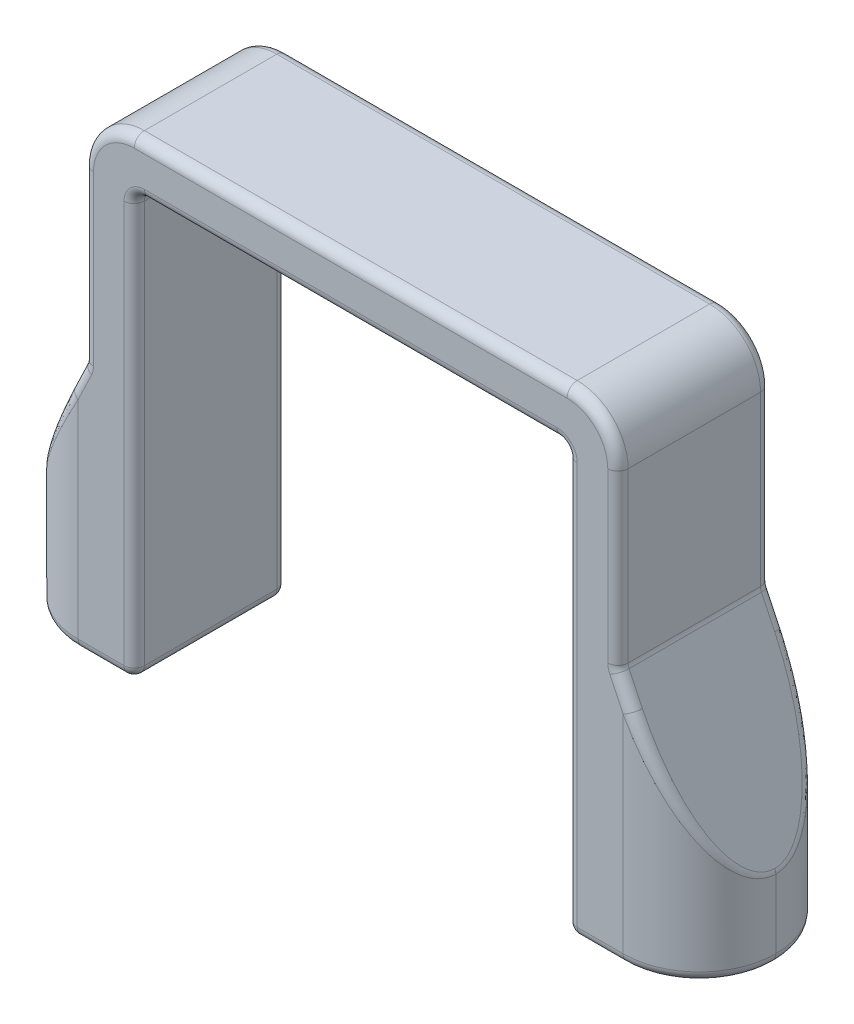
SolidWorks part; units mm, degrees
ref_plane "Front Plane" through (0, 0, 0) normal (0, 0, 1) x (1, 0, 0)
ref_plane "Top Plane" through (0, 0, 0) normal (0, 1, 0) x (1, 0, 0)
ref_plane "Right Plane" through (0, 0, 0) normal (1, 0, 0) x (0, 0, -1)
sketch "Sketch2" plane through (0, 0, 0) normal (0, 0, 1) x (1, 0, 0)
  line L0 (34.25, -20.75) -> (34.25, -12.75)
  line L5 (21.25, -20.75) -> (-21.25, -20.75)
  line L6 (0, -20.75) -> (0, 20.75) construction
  line L11 (21.25, 20.75) -> (-21.25, 20.75)
  line L12 (-21.25, -20.75) -> (-21.25, 20.75)
  line L13 (-26.25, 25.75) -> (26.25, 25.75)
  line L14 (-26.25, 25.75) -> (-26.25, 20.75)
  line L15 (-26.25, 20.75) -> (26.25, 20.75)
  line L16 (0, 25.75) -> (0, 20.75)
  line L17 (-21.25, -20.75) -> (-26.25, -20.75)
  line L18 (-21.25, -20.75) -> (-21.25, 20.75)
  line L19 (-21.25, 20.75) -> (-26.25, 20.75)
  line L20 (-26.25, -20.75) -> (-26.25, 20.75)
  line L21 (-26.25, -20.75) -> (-34.25, -20.75)
  line L22 (-26.25, -20.75) -> (-26.25, -12.75)
  line L23 (-26.25, -12.75) -> (-34.25, -12.75)
  line L24 (-34.25, -20.75) -> (-34.25, -12.75)
  line L25 (26.25, -12.75) -> (34.25, -12.75)
  line L26 (26.25, -20.75) -> (26.25, -12.75)
  line L27 (26.25, -20.75) -> (34.25, -20.75)
  line L28 (26.25, -20.75) -> (26.25, 20.75)
  line L29 (21.25, 20.75) -> (26.25, 20.75)
  line L30 (21.25, -20.75) -> (21.25, 20.75)
  line L31 (21.25, -20.75) -> (26.25, -20.75)
  line L32 (26.25, 25.75) -> (26.25, 20.75)
  line L33 (21.25, -20.75) -> (21.25, 20.75)
  line L34 (-34.25, -12.75) -> (-26.25, 4)
  line L35 (34.25, -12.75) -> (26.25, 4)
  point P4 (0, 0)
  dimension "D1" = 21.25
  dimension "D2" = 41.5
  dimension "D3" = 5
  dimension "D4" = 5
  dimension "D5" = 8
  dimension "D6" = 8
  dimension "D7" = 16.75
extrude "Boss-Extrude1" add sketch "Sketch2" along normal blind 15 contours L24 L21 L20 L23 | L20 L17 L12 L15 | L16 L13 L14 L15 | L32 L13 L16 L11 L15 | L30 L31 L26 L28 L15 | L26 L27 L0 L25 | L34 L23 L20 | L25 L35 L28 region at (30.25, -16.75, 0) region at (28.9167, -7.1667, 0) region at (23.75, 0, 0) region at (13.125, 23.25, 0) region at (-23.75, 0, 0) region at (-13.125, 23.25, 0) region at (-30.25, -16.75, 0) region at (-28.9167, -7.1667, 0)
sketch "Sketch3" plane through (0, -20.75, 0) normal (0, -1, 0) x (1, 0, 0)
  line L0 (0, 15) -> (0, 0) construction
  line L1 (-21.25, 15) -> (21.25, 15) construction
  line L3 (-21.25, 15) -> (-34.25, 15) construction
  line L4 (-34.25, 15) -> (-34.25, 0) construction
  circle A0 centre (-28.25, 7.5) radius 3.25
  circle A1 centre (28.25, 7.5) radius 3.25
  dimension "D1" = 6
  dimension "D2" = 6.5
  dimension "D3" = 7.5
  dimension "D4" = 28.25
extrude "Cut-Extrude1" cut sketch "Sketch3" against normal blind 10
fillet "Fillet1" radius 7.5 4 edges at (-34.25, -16.75, 15) (-34.25, -16.75, 0) (34.25, -16.75, 15) (34.25, -16.75, 0)
fillet "Fillet2" radius 5 2 edges at (26.25, 25.75, 7.5) (-26.25, 25.75, 7.5)
fillet "Fillet18" radius 1 40 edges at (26.5, 3.4766, 0) (26.25, 12.375, 0) (0, 25.75, 0) (-26.5, 3.4766, 0) (-21.25, 0, 0) (26.25, 4, 7.5) (32.0533, -8.1507, 2.1967) (24.7855, 24.2855, 0) (28.25, -20.75, 10.75) (-28.25, -20.75, 4.25) (-26.25, 12.375, 0) (-24, -20.75, 0) (0, 20.75, 0) (21.25, 0, 0) (24, -20.75, 0) (26.5, 3.4766, 15) (26.25, 12.375, 15) (0, 25.75, 15) (-26.25, 12.375, 15) (-26.5, 3.4766, 15) (-24, -20.75, 15) (-21.25, 0, 15) (0, 20.75, 15) (21.25, 0, 15) (24, -20.75, 15) (21.25, -20.75, 7.5) (21.25, 20.75, 7.5) (-21.25, 20.75, 7.5) (-21.25, -20.75, 7.5) (-26.25, 4, 7.5) (-32.0533, -8.1507, 2.1967) (-32.0533, -8.1507, 12.8033) (-32.0533, -20.75, 2.1967) (-32.0533, -20.75, 12.8033) (32.0533, -8.1507, 12.8033) (32.0533, -20.75, 2.1967) (32.0533, -20.75, 12.8033) (-24.7855, 24.2855, 0) (-24.7855, 24.2855, 15) (24.7855, 24.2855, 15)
equation "\"D7@Sketch2\"=(\"D2@Sketch2\"-\"D6@Sketch2\")/2"
